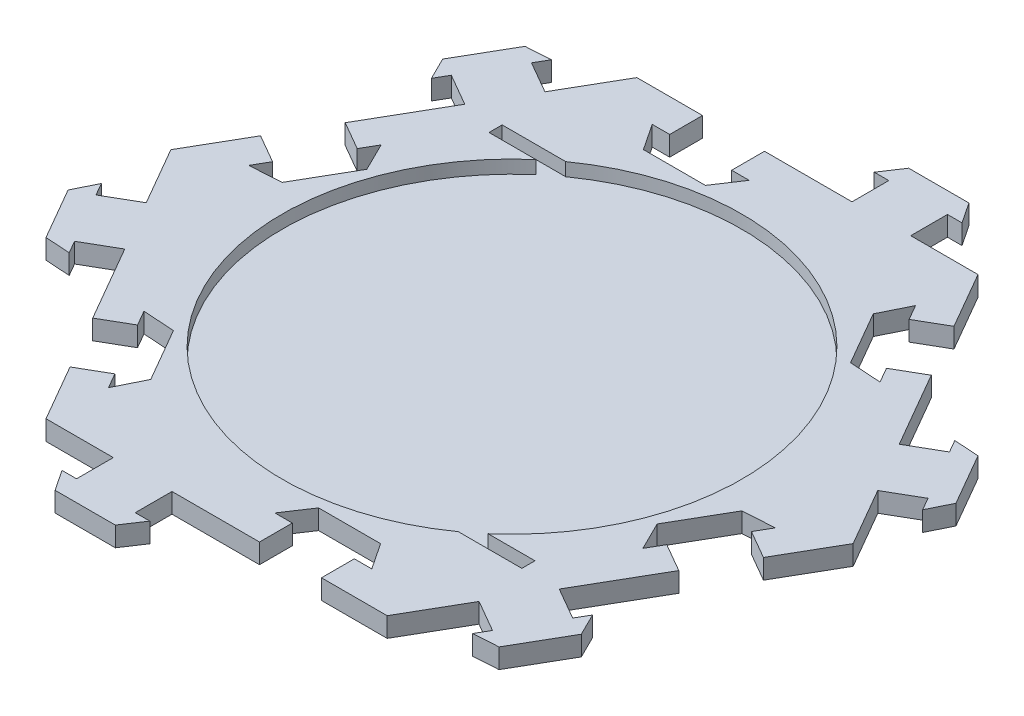
SolidWorks part; units mm, degrees
ref_plane "Front Plane" through (0, 0, 0) normal (0, 0, 1) x (1, 0, 0)
ref_plane "Top Plane" through (0, 0, 0) normal (0, 1, 0) x (1, 0, 0)
ref_plane "Right Plane" through (0, 0, 0) normal (1, 0, 0) x (0, 0, -1)
sketch "Sketch1" plane through (0, 0, 0) normal (0, 1, 0) x (1, 0, 0)
  line L0 (-15.9808, 45) -> (-15.9808, 40)
  line L1 (25.9808, -45) -> (51.9615, 0)
  line L2 (51.9615, 0) -> (25.9808, 45)
  line L3 (25.9808, 45) -> (-25.9808, 45)
  line L4 (-25.9808, 45) -> (-51.9615, 0)
  line L5 (-51.9615, 0) -> (-25.9808, -45)
  line L6 (-25.9808, -45) -> (25.9808, -45)
  line L7 (-15.9808, 40) -> (-18.6446, 40)
  line L8 (-18.6446, 40) -> (-15.9808, 36)
  line L9 (-15.9808, 36) -> (-6.5403, 36)
  line L10 (-6.5403, 36) -> (-3.8765, 40)
  line L11 (-3.8765, 40) -> (-6.5403, 40)
  line L12 (-6.5403, 40) -> (-6.5403, 45)
  line L13 (-15.9808, 40) -> (-15.9808, 36) construction
  line L14 (6.5403, 45) -> (6.5403, 50) construction
  line L15 (6.5403, 50) -> (3.8765, 50) construction
  line L16 (3.8765, 50) -> (6.5403, 54) construction
  line L17 (6.5403, 54) -> (15.9808, 54) construction
  line L18 (15.9808, 54) -> (18.6446, 50) construction
  line L19 (18.6446, 50) -> (15.9808, 50) construction
  line L20 (15.9808, 50) -> (15.9808, 45) construction
  line L21 (6.5403, 50) -> (6.5403, 54) construction
  line L22 (6.7903, 50.25) -> (6.7903, 45)
  line L23 (6.7903, 50.25) -> (4.3433, 50.25) construction
  line L24 (4.3433, 50.25) -> (6.6742, 53.75) construction
  line L25 (6.6742, 53.75) -> (15.8469, 53.75) construction
  line L26 (15.8469, 53.75) -> (18.1777, 50.25) construction
  line L27 (18.1777, 50.25) -> (15.7308, 50.25) construction
  line L28 (15.7308, 50.25) -> (15.7308, 45)
  line L29 (15.7308, 50.25) -> (15.7308, 50.6)
  line L30 (7.0097, 50.6) -> (4.5764, 50.6)
  line L31 (4.5764, 50.6) -> (6.6742, 53.75)
  line L32 (6.6742, 53.75) -> (15.8469, 53.75)
  line L33 (15.8469, 53.75) -> (17.9446, 50.6)
  line L34 (17.9446, 50.6) -> (15.5089, 50.6)
  line L35 (6.7903, 50.25) -> (6.7903, 50.6)
  line L36 (30.9808, 36.3397) -> (26.6506, 33.8397)
  line L37 (26.6506, 33.8397) -> (25.3187, 36.1467)
  line L38 (25.3187, 36.1467) -> (23.1865, 31.8397)
  line L39 (23.1865, 31.8397) -> (27.9068, 23.664)
  line L40 (27.9068, 23.664) -> (32.7028, 23.3571)
  line L41 (32.7028, 23.3571) -> (31.3709, 25.664)
  line L42 (31.3709, 25.664) -> (35.701, 28.164)
  line L43 (51.3832, 11.5018) -> (46.8365, 8.8768)
  line L44 (46.9129, 19.2444) -> (42.3663, 16.6194)
  line L45 (46.9129, 19.2444) -> (47.216, 19.4194)
  line L46 (51.3832, 11.5018) -> (51.6863, 11.6768)
  line L47 (52.7932, 9.7595) -> (51.5754, 11.8689)
  line L48 (54.4723, 13.1512) -> (52.7932, 9.7595)
  line L49 (49.8859, 21.095) -> (54.4723, 13.1512)
  line L50 (46.1091, 21.3367) -> (49.8859, 21.095)
  line L51 (47.3257, 19.2294) -> (46.1091, 21.3367)
  line L52 (46.9615, -8.6603) -> (42.6314, -6.1603)
  line L53 (42.6314, -6.1603) -> (43.9633, -3.8533)
  line L54 (43.9633, -3.8533) -> (39.1673, -4.1603)
  line L55 (39.1673, -4.1603) -> (34.4471, -12.336)
  line L56 (34.4471, -12.336) -> (36.5793, -16.6429)
  line L57 (36.5793, -16.6429) -> (37.9112, -14.336)
  line L58 (37.9112, -14.336) -> (42.2413, -16.836)
  line L59 (35.6524, -38.7482) -> (31.1058, -36.1232)
  line L60 (40.1226, -31.0056) -> (35.576, -28.3806)
  line L61 (40.1226, -31.0056) -> (40.4257, -31.1806)
  line L62 (35.6524, -38.7482) -> (35.9555, -38.9232)
  line L63 (34.8486, -40.8405) -> (36.0664, -38.7311)
  line L64 (38.6254, -40.5988) -> (34.8486, -40.8405)
  line L65 (43.2118, -32.655) -> (38.6254, -40.5988)
  line L66 (41.5327, -29.2633) -> (43.2118, -32.655)
  line L67 (40.316, -31.3706) -> (41.5327, -29.2633)
  line L68 (15.9808, -45) -> (15.9808, -40)
  line L69 (15.9808, -40) -> (18.6446, -40)
  line L70 (18.6446, -40) -> (15.9808, -36)
  line L71 (15.9808, -36) -> (6.5403, -36)
  line L72 (6.5403, -36) -> (3.8765, -40)
  line L73 (3.8765, -40) -> (6.5403, -40)
  line L74 (6.5403, -40) -> (6.5403, -45)
  line L75 (-15.7308, -50.25) -> (-15.7308, -45)
  line L76 (-6.7903, -50.25) -> (-6.7903, -45)
  line L77 (-6.7903, -50.25) -> (-6.7903, -50.6)
  line L78 (-15.7308, -50.25) -> (-15.7308, -50.6)
  line L79 (-17.9446, -50.6) -> (-15.5089, -50.6)
  line L80 (-15.8469, -53.75) -> (-17.9446, -50.6)
  line L81 (-6.6742, -53.75) -> (-15.8469, -53.75)
  line L82 (-4.5764, -50.6) -> (-6.6742, -53.75)
  line L83 (-7.0097, -50.6) -> (-4.5764, -50.6)
  line L84 (-30.9808, -36.3397) -> (-26.6506, -33.8397)
  line L85 (-26.6506, -33.8397) -> (-25.3187, -36.1467)
  line L86 (-25.3187, -36.1467) -> (-23.1865, -31.8397)
  line L87 (-23.1865, -31.8397) -> (-27.9068, -23.664)
  line L88 (-27.9068, -23.664) -> (-32.7028, -23.3571)
  line L89 (-32.7028, -23.3571) -> (-31.3709, -25.664)
  line L90 (-31.3709, -25.664) -> (-35.701, -28.164)
  line L91 (-51.3832, -11.5018) -> (-46.8365, -8.8768)
  line L92 (-46.9129, -19.2444) -> (-42.3663, -16.6194)
  line L93 (-46.9129, -19.2444) -> (-47.216, -19.4194)
  line L94 (-51.3832, -11.5018) -> (-51.6863, -11.6768)
  line L95 (-52.7932, -9.7595) -> (-51.5754, -11.8689)
  line L96 (-54.4723, -13.1512) -> (-52.7932, -9.7595)
  line L97 (-49.8859, -21.095) -> (-54.4723, -13.1512)
  line L98 (-46.1091, -21.3367) -> (-49.8859, -21.095)
  line L99 (-47.3257, -19.2294) -> (-46.1091, -21.3367)
  line L100 (-46.9615, 8.6603) -> (-42.6314, 6.1603)
  line L101 (-42.6314, 6.1603) -> (-43.9633, 3.8533)
  line L102 (-43.9633, 3.8533) -> (-39.1673, 4.1603)
  line L103 (-39.1673, 4.1603) -> (-34.4471, 12.336)
  line L104 (-34.4471, 12.336) -> (-36.5793, 16.6429)
  line L105 (-36.5793, 16.6429) -> (-37.9112, 14.336)
  line L106 (-37.9112, 14.336) -> (-42.2413, 16.836)
  line L107 (-35.6524, 38.7482) -> (-31.1058, 36.1232)
  line L108 (-40.1226, 31.0056) -> (-35.576, 28.3806)
  line L109 (-40.1226, 31.0056) -> (-40.4257, 31.1806)
  line L110 (-35.6524, 38.7482) -> (-35.9555, 38.9232)
  line L111 (-34.8486, 40.8405) -> (-36.0664, 38.7311)
  line L112 (-38.6254, 40.5988) -> (-34.8486, 40.8405)
  line L113 (-43.2118, 32.655) -> (-38.6254, 40.5988)
  line L114 (-41.5327, 29.2633) -> (-43.2118, 32.655)
  line L115 (-40.316, 31.3706) -> (-41.5327, 29.2633)
  line L116 (6.7903, 45) -> (6.7903, 50.25) construction
  line L117 (15.7308, 50.25) -> (15.7308, 45) construction
  line L118 (0, 5) -> (0, -2) construction
  line L119 (2.5, -2) -> (0, 5)
  line L120 (0, 5) -> (-2.5, -2)
  line L121 (-2.5, -2) -> (2.5, -2)
  circle A0 centre (0, 0) radius 45 construction
  circle A1 centre (0, 0) radius 45 construction
  circle A2 centre (0, 0) radius 35
  point P145 (0, 0)
  point P146 (-0.0013, -0.0009)
  dimension "D1" = 90
  dimension "D4" = 10
  dimension "D2" = 5
  dimension "D3" = 4
  dimension "D5" = 10
  dimension "D6" = 0.25
  dimension "D7" = 0.35
  dimension "D8" = 6
  dimension "D10" = 0.6
  dimension "D9" = 0.25
  dimension "D12" = 5
  dimension "D13" = 7
  dimension "D14" = 2
  dimension "D11" = 10
extrude "Boss-Extrude1" add sketch "Sketch1" along normal blind 3 contours L2 L3 L4 | L3 | L2 | L4 | L1 | L5 | L6 region at (-17.3555, 0, -42.5) region at (11.2605, 0, -49.5746) region at (-37.3026, 0, -34.5392) region at (48.5631, 0, -15.0354) region at (-48.5631, 0, 15.0354) region at (37.3026, 0, 34.5392) region at (-11.2605, 0, 49.5746)
extrude "Boss-Extrude2" add sketch "Sketch1<3>" along normal blind 1 contours A2 | L120 L121 L119 region at (0, 0, -0.3333) region at (-34.0101, 0, 0)
sketch "Sketch1<3>" plane through (0, 0, 0) normal (0, 1, 0) x (1, 0, 0) same geometry as "Sketch1"
sketch "Sketch2" plane through (0, 1, 0) normal (0, 1, 0) x (1, 0, 0)
  line L0 (0, 27.5) -> (0, -27.5) construction
  line L1 (0, 27.5) -> (-30, 27.5)
  line L2 (0, -27.5) -> (30, -27.5)
  dimension "D1" = 55
  dimension "D2" = 30
extrude "Cut-Extrude-Thin1" cut sketch "Sketch2" along normal blind 10 thin contours L2 | L1 thin type mid plane wall 2
